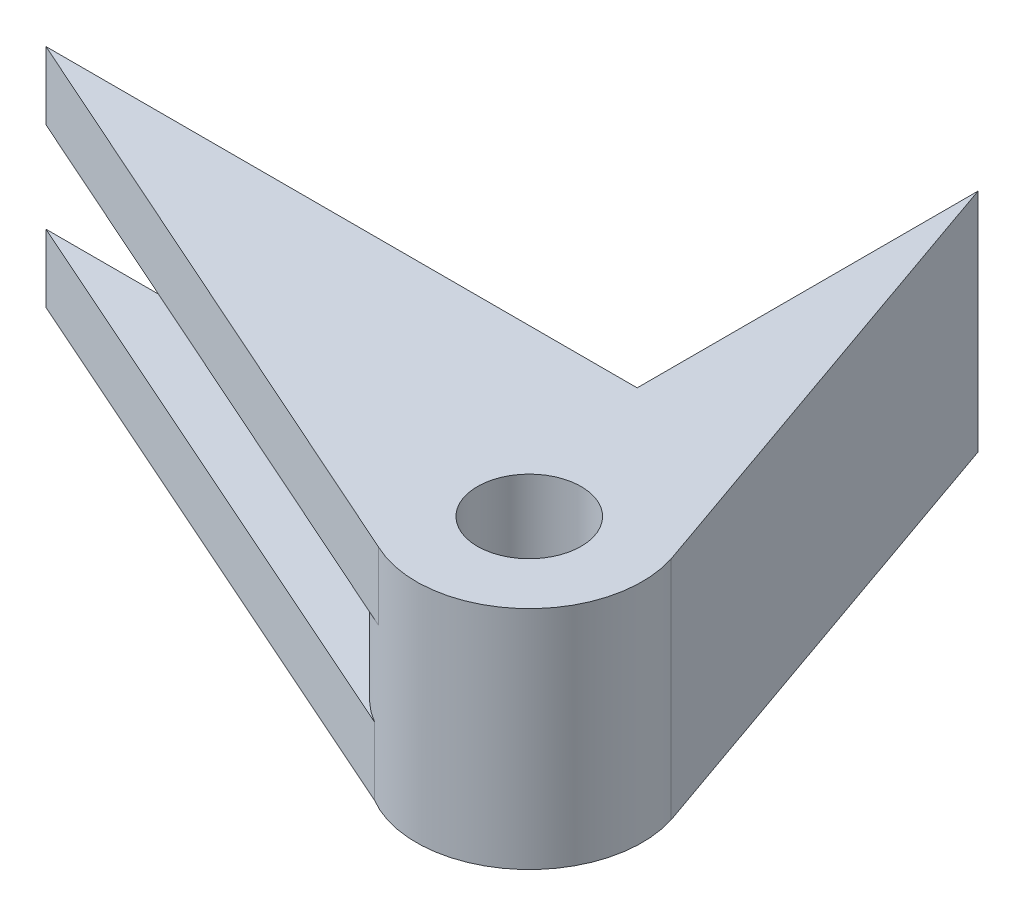
SolidWorks part; units mm, degrees
ref_plane "Front Plane" through (0, 0, 0) normal (0, 0, 1) x (1, 0, 0)
ref_plane "Top Plane" through (0, 0, 0) normal (0, 1, 0) x (1, 0, 0)
ref_plane "Right Plane" through (0, 0, 0) normal (1, 0, 0) x (0, 0, -1)
sketch "Sketch1" plane through (0, 0, 0) normal (0, 1, 0) x (1, 0, 0)
  line L0 (30.5988, 30.1673) -> (30.5988, 0)
  line L1 (30.5988, 30.1673) -> (45.2163, -11.6217)
  line L2 (0, 0) -> (-21.7254, 0)
  line L3 (-21.7254, 0) -> (30.5988, -23.2433)
  line L4 (30.5988, 0) -> (0, 0)
  line L5 (25.6797, -14.6303) -> (25.6797, 0)
  circle A0 centre (35.6797, -14.6303) radius 10
  circle A1 centre (35.6797, -14.6303) radius 4.5901
  dimension "20" = 20
extrude "Boss-Extrude1" add sketch "Sketch1" along normal blind 6 contours A0 L5 L4 L2 L3 | A0 L1 L0 L4 L5 | L1 A0 A1 region at (33.7974, 0, -4.5999) region at (44.8474, 0, 11.4234) region at (10.1124, 0, 7.2013)
extrude "Boss-Extrude2" add sketch "Sketch1<3>" along normal blind 20 contours A0 A1 | A0 L1 L0 L4 L5 region at (33.7974, 0, -4.5999) region at (44.8474, 0, 11.4234)
sketch "Sketch1<3>" plane through (0, 0, 0) normal (0, 1, 0) x (1, 0, 0) same geometry as "Sketch1"
sketch "Sketch2" plane through (0, 20, 0) normal (0, 1, 0) x (1, 0, 0)
  line L0 (45.2163, -11.6217) -> (30.5988, 30.1673)
  line L1 (-21.7254, 0) -> (30.5988, 0)
  line L2 (30.5988, 0) -> (30.5988, 30.1673)
  line L4 (30.5988, 30.1673) -> (45.2163, -11.6217) construction
  line L6 (-21.7254, 0) -> (31.8573, -23.8709)
  circle A0 centre (35.6797, -14.6303) radius 10
  arc A1 (25.6797, -14.6303) -> (45.2163, -11.6217) centre (35.6797, -14.6303) ccw construction
  point P2 (30.6688, 29.967)
  point P13 (45.2114, -11.6074)
  point P17 (30.5988, 0)
  arc M3 (25.6797, -14.6303) -> (45.2163, -11.6217) centre (35.6797, -14.6303) ccw
extrude "Boss-Extrude3" add sketch "Sketch2" against normal blind 6 contours L1 L6 L0 L2 M3 region at (18.2453, 20, 3.172)
